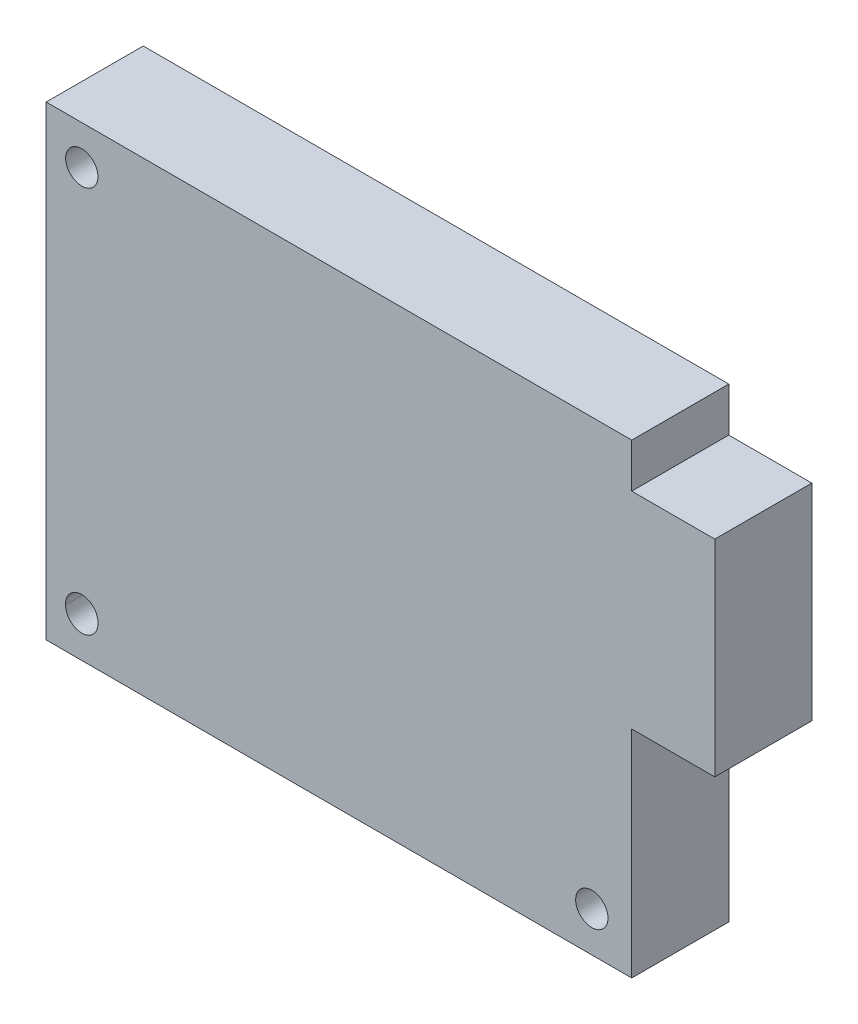
SolidWorks part; units mm, degrees
ref_plane "Plan de face" through (0, 0, 0) normal (0, 0, 1) x (1, 0, 0)
ref_plane "Plan de dessus" through (0, 0, 0) normal (0, 1, 0) x (1, 0, 0)
ref_plane "Plan de droite" through (0, 0, 0) normal (1, 0, 0) x (0, 0, -1)
sketch "Esquisse1" plane through (0, 0, 0) normal (0, 0, 1) x (1, 0, 0)
  line L0 (27.15, 17.5) -> (34.85, 17.5)
  line L1 (-27.15, 21.6) -> (27.15, 21.6)
  line L2 (-27.15, 21.6) -> (-27.15, -21.6)
  line L3 (-27.15, -21.6) -> (27.15, -21.6)
  line L4 (27.15, 21.6) -> (27.15, 17.5)
  line L5 (-27.15, 21.6) -> (27.15, -21.6) construction
  line L6 (-27.15, -21.6) -> (27.15, 21.6) construction
  line L7 (34.85, 17.5) -> (34.85, -1.6)
  line L8 (34.85, -1.6) -> (27.15, -1.6)
  line L9 (27.15, -1.6) -> (27.15, -21.6)
  point P0 (0, 0)
  dimension "D1" = 54.3
  dimension "D2" = 43.2
  dimension "D3" = 19.1
  dimension "D4" = 4.1
  dimension "D5" = 62
extrude "Boss.-Extru.1" add sketch "Esquisse1" along normal blind 9
hole_wizard "Dégagement M3.51" positions "Esquisse2" profile "Esquisse3" hole size "M3.5" standard "Ansi Metric" end condition up to next
sketch "Esquisse2" plane through (0, 0, 9) normal (0, 0, 1) x (1, 0, 0)
  line L0 (27.15, -21.6) -> (27.15, -1.6) construction
  line L1 (-27.15, -21.6) -> (27.15, -21.6) construction
  point P0 (-23.85, 18)
  point P2 (-23.85, -17.9)
  point P4 (-23.85, -17.8)
  point P7 (23.45, -17.9)
  dimension "D1" = 47.3
  dimension "D2" = 35.9
  dimension "D3" = 3.7
  dimension "D4" = 3.7
sketch "Esquisse3" plane through (-23.85, 18, 9) normal (1, 0, 0) x (0, -1, 0)
  line L0 (0, 0) -> (0, 9)
  line L1 (0, 9) -> (1.5, 9)
  line L2 (1.5, 9) -> (1.5, 0)
  line L5 (1.5, 0) -> (0, 0)
  line L11 (0, -6.35) -> (0, 107.95) construction
  dimension "Diamètre du perçage jusqu'au prochain" = 3
  dimension "Profondeur du perçage jusqu'au prochain" = 9
